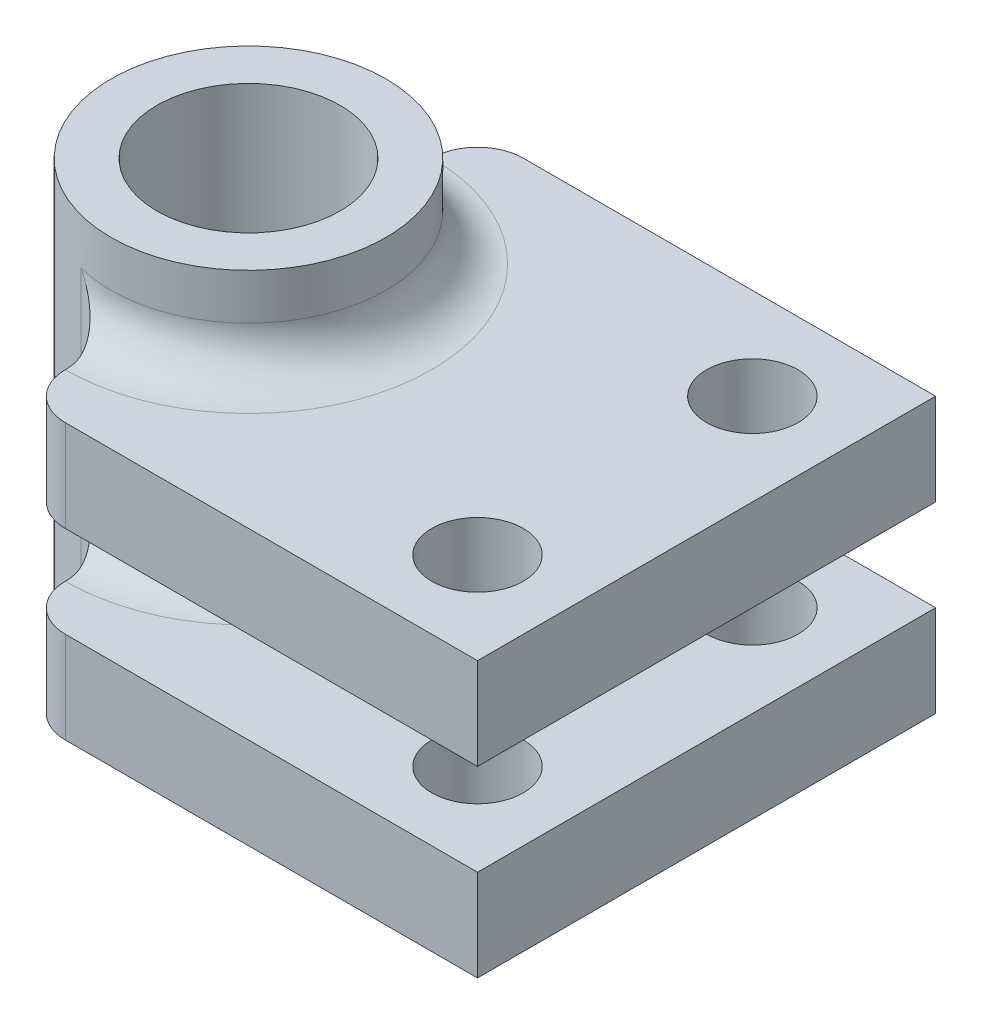
SolidWorks part; units mm, degrees
ref_plane "Front Plane" through (0, 0, 0) normal (0, 0, 1) x (1, 0, 0)
ref_plane "Top Plane" through (0, 0, 0) normal (0, 1, 0) x (1, 0, 0)
ref_plane "Right Plane" through (0, 0, 0) normal (1, 0, 0) x (0, 0, -1)
sketch "Sketch2" plane through (0, 0, 0) normal (0, 1, 0) x (1, 0, 0)
  circle A0 centre (0, 0) radius 15
  circle A1 centre (0, 0) radius 10
  dimension "D1" = 30
  dimension "D2" = 20
extrude "Boss-Extrude1" add sketch "Sketch2" along normal blind 50
sketch "Sketch3" plane through (0, 0, 0) normal (0, 0, 1) x (1, 0, 0)
  line L0 (0, 40) -> (50, 40)
  line L1 (50, 40) -> (50, 30)
  line L2 (50, 30) -> (0, 30)
  line L3 (0, 30) -> (0, 40)
  line L4 (0, 10) -> (0, 20)
  line L5 (0, 20) -> (50, 20)
  line L6 (50, 20) -> (50, 10)
  line L7 (50, 10) -> (0, 10)
  line L9 (15, 50) -> (-15, 50) construction
  line L10 (-15, 0) -> (15, 0) construction
  dimension "D1" = 50
  dimension "D2" = 50
  dimension "D3" = 10
  dimension "D4" = 10
  dimension "D5" = 10
  dimension "D6" = 10
extrude "Boss-Extrude2" add sketch "Sketch3" along normal blind 25 and the other way blind 25
sketch "Sketch4" plane through (0, 0, 0) normal (0, 1, 0) x (1, 0, 0)
  line L0 (0, 10) -> (0, -10) construction
  circle A0 centre (0, 0) radius 10
extrude "Cut-Extrude1" cut sketch "Sketch4" along normal through all both
fillet "Fillet2" radius 5 12 edges at (15, 40, 0) (15, 30, 0) (15, 10, 0) (15, 20, 0) (0, 15, -15) (0, 35, -15) (0, 15, -25) (0, 35, -25) (0, 15, 15) (0, 35, 15) (0, 15, 25) (0, 35, 25)
sketch "Sketch5" plane through (0, 0, 0) normal (0, 1, 0) x (1, 0, 0)
  line L0 (50, 25) -> (50, -25) construction
  line L1 (50, 25) -> (5, 25) construction
  line L2 (50, -25) -> (5, -25) construction
  circle A0 centre (40, 15) radius 5
  circle A1 centre (40, -15) radius 5
  dimension "D1" = 10
  dimension "D2" = 10
  dimension "D3" = 10
  dimension "D4" = 10
  dimension "D5" = 10
  dimension "D6" = 10
extrude "Cut-Extrude2" cut sketch "Sketch5" along normal through all both
